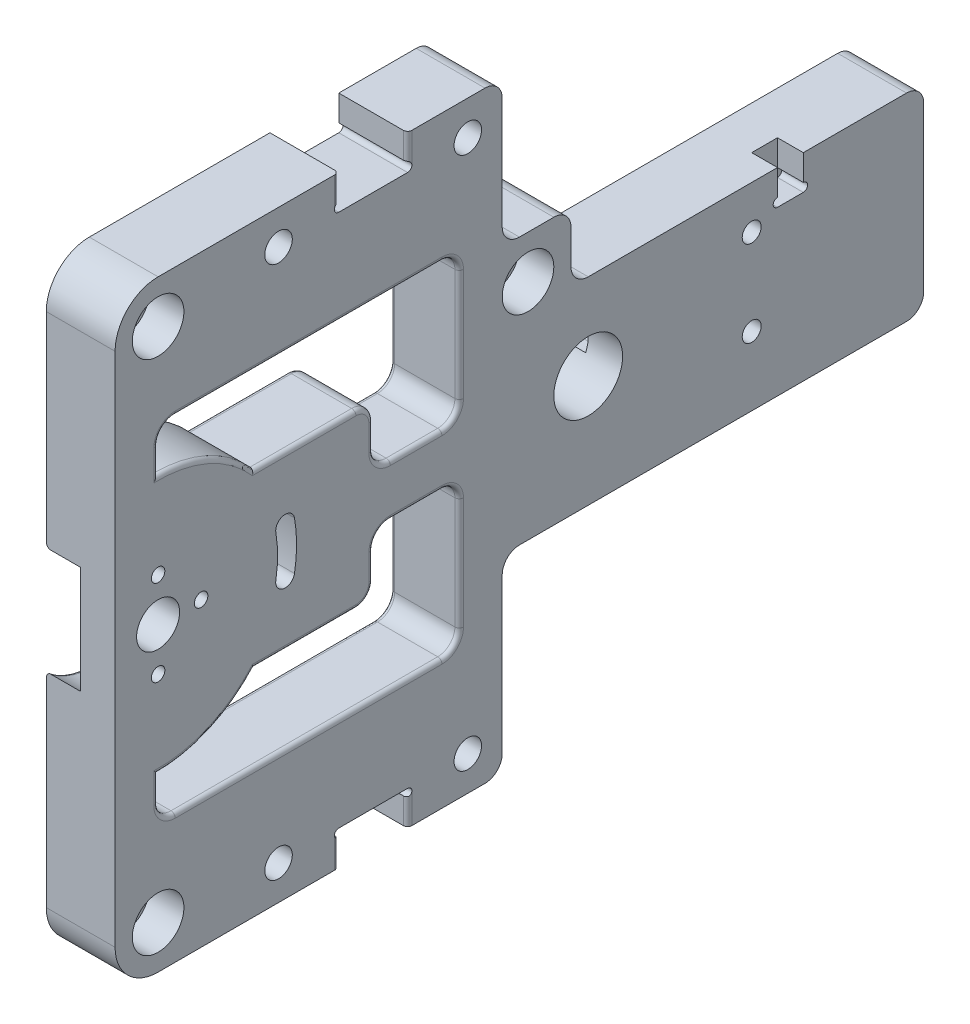
SolidWorks part; units mm, degrees
material "6061 Alloy"
ref_plane "Front Plane" through (0, 0, 0) normal (0, 0, 1) x (1, 0, 0)
ref_plane "Top Plane" through (0, 0, 0) normal (0, 1, 0) x (1, 0, 0)
ref_plane "Right Plane" through (0, 0, 0) normal (1, 0, 0) x (0, 0, -1)
sketch "Sketch1" plane through (0, 0, 0) normal (1, 0, 0) x (0, 0, -1)
  line L0 (-40, 0) -> (40, 0) construction
  line L1 (-40, 35) -> (5, 35)
  line L2 (-40, 35) -> (-40, -35)
  line L3 (-40, -35) -> (5, -35)
  line L4 (54, 10) -> (54, -13)
  line L15 (10, 0) -> (20, 0) construction
  line L18 (54, 10) -> (13, 10)
  line L19 (5, 35) -> (5, 18)
  line L22 (54, -13) -> (5, -13)
  line L23 (5, -35) -> (5, -13)
  line L24 (10, 1.5) -> (20, 1.5)
  line L25 (10, -1.5) -> (20, -1.5)
  line L26 (-25, 35) -> (-40, 35)
  line L33 (5, 18) -> (13, 18)
  line L34 (13, 10) -> (13, 18)
  circle A0 centre (15, 0) radius 4
  arc A1 (10, 1.5) -> (10, -1.5) centre (10, 0) ccw
  arc A2 (20, -1.5) -> (20, 1.5) centre (20, 0) ccw
  circle A3 centre (-35, 0) radius 2.5
  arc A4 (-40, -6.245) -> (-40, 6.245) centre (-35, 0) ccw
  circle A5 centre (-35, 5) radius 0.7835
  circle A6 centre (-30, 0) radius 0.7835
  circle A7 centre (-35, -5) radius 0.7835
  point P0 (0, 0)
  point P24 (15, 0)
  dimension "D9" = 8
  dimension "D10" = 1.5
  dimension "D14" = 5
  dimension "D15" = 16
  dimension "D2" = 1.567
  dimension "D3" = 10
  dimension "D4" = 13
  dimension "D5" = 45
  dimension "D7" = 45
  dimension "D11" = 5
  dimension "D12" = 55
  dimension "D13" = 5
  dimension "D16" = 5
  dimension "D17" = 5
  dimension "D18" = 5
  dimension "D19" = 49
  dimension "D20" = 70
  dimension "D21" = 40
  dimension "D22" = 35
  dimension "D23" = 8
  dimension "D24" = 8
extrude "Boss-Extrude1" add sketch "Sketch1" along normal blind 8 contours L2 L3 L23 L22 L4 L18 L34 L33 L19 L1
extrude "Cut-Extrude1" cut sketch "Sketch1<3>" along normal blind 8 contours A0
sketch "Sketch1<3>" plane through (0, 0, 0) normal (1, 0, 0) x (0, 0, -1) same geometry as "Sketch1"
extrude "Cut-Extrude2" cut sketch "Sketch1<4>" along normal blind 4 contours A2 L24 A1 L25
sketch "Sketch1<4>" plane through (0, 0, 0) normal (1, 0, 0) x (0, 0, -1) same geometry as "Sketch1"
extrude "Cut-Extrude3" cut sketch "Sketch1<5>" along normal blind 4 contours L2 A4 A3 region at (0, 0, 27.2062)
sketch "Sketch1<5>" plane through (0, 0, 0) normal (1, 0, 0) x (0, 0, -1) same geometry as "Sketch1"
extrude "Cut-Extrude4" cut sketch "Sketch1<6>" along normal blind 8 contours A3 | A7 | A6 | A5
sketch "Sketch1<6>" plane through (0, 0, 0) normal (1, 0, 0) x (0, 0, -1) same geometry as "Sketch1"
fillet "Fillet1" radius 2 8 edges at (4, -35, -5) (4, -13, -5) (4, -13, -54) (4, 10, -54) (4, 35, -5) (4, 10, -13) (4, 18, -13) (4, 18, -5)
fillet "Fillet7" radius 5 2 edges at (4, -35, 40) (4, 35, 40)
sketch "Sketch3" plane through (0, 0, 0) normal (-1, 0, 0) x (0, 0, 1)
  line L0 (-54, 8) -> (-54, -11) construction
  line L3 (0, 0) -> (-54, 0) construction
  circle A0 centre (-34, 5) radius 2
  circle A1 centre (-34, -5) radius 2
  circle A2 centre (-34, -5) radius 1.1
  circle A3 centre (-34, 5) radius 1.1
  dimension "D1" = 4
  dimension "D2" = 2.2
  dimension "D5" = 20
  dimension "D6" = 5
  dimension "D7" = 5
extrude "Cut-Extrude6" cut sketch "Sketch3" against normal blind 4 contours A0 | A1
extrude "Cut-Extrude7" cut sketch "Sketch3<3>" against normal blind 8 contours A3 | A2
sketch "Sketch3<3>" plane through (0, 0, 0) normal (-1, 0, 0) x (0, 0, 1) same geometry as "Sketch3"
fillet "Fillet3" radius 0.5 1 edges at (0, 0, 27)
sketch "Sketch4" plane through (0, 0, 0) normal (-1, 0, 0) x (0, 0, 1)
  line L0 (10, 10) -> (10, 3)
  line L1 (40, 6.245) -> (40, -6.245) construction
  line L2 (-44.1333, 0) -> (39.9934, 0) construction
  line L6 (10, 10) -> (23.8197, 10)
  line L7 (10, -10) -> (23.8197, -10)
  line L8 (35, 15) -> (35, 20)
  line L9 (35, 20) -> (0, 20)
  line L10 (0, 20) -> (0, 3)
  line L11 (0, -20) -> (35, -20)
  line L12 (35, -20) -> (35, -15)
  line L13 (10, 3) -> (0, 3)
  line L14 (10, -3) -> (0, -3)
  line L15 (10, -3) -> (10, -10)
  line L16 (0, -3) -> (0, -20)
  arc A2 (35, 15) -> (23.8197, 10) centre (35, 0) ccw
  arc A4 (23.8197, -10) -> (35, -15) centre (35, 0) ccw
  dimension "D2" = 20
  dimension "D4" = 30
  dimension "D1" = 30
  dimension "D3" = 10
  dimension "D5" = 5
  dimension "D6" = 35
  dimension "D7" = 3
  dimension "D8" = 3
extrude "Cut-Extrude8" cut sketch "Sketch4" against normal blind 10
fillet "Fillet4" radius 2 10 edges at (4, -20, 0) (4, -20, 35) (4, -10, 10) (4, -3, 0) (4, -3, 10) (4, 20, 35) (4, 20, 0) (4, 3, 0) (4, 3, 10) (4, 10, 10)
fillet "Fillet5" radius 0.5 48 edges at (8, -16.5, 35) (8, -19.4142, 34.4142) (8, -20, 17.5) (8, -19.4142, 0.5858) (8, -11.5, 0) (8, -3.5858, 0.5858) (8, -3, 5) (8, -3.5858, 9.4142) (8, -6.5, 10) (8, -9.4142, 10.5858) (0, -16.5, 35) (0, -19.4142, 34.4142) (0, -20, 17.5) (0, -19.4142, 0.5858) (0, -11.5, 0) (0, -3.5858, 0.5858) (0, -3, 5) (0, -3.5858, 9.4142) (0, -6.5, 10) (0, -9.4142, 10.5858) (8, 16.5, 35) (8, 19.4142, 34.4142) (8, 20, 17.5) (8, 19.4142, 0.5858) (8, 11.5, 0) (8, 3.5858, 0.5858) (8, 3, 5) (8, 3.5858, 9.4142) (8, 6.5, 10) (8, 9.4142, 10.5858) (0, 16.5, 35) (0, 19.4142, 34.4142) (0, 10, 17.9098) (0, 9.4142, 10.5858) (0, 6.5, 10) (0, 3.5858, 9.4142) (0, 3, 5) (0, 3.5858, 0.5858) (0, 11.5, 0) (0, 19.4142, 0.5858) (8, -10, 17.9098) (8, -13.6931, 28.8763) (0, -10, 17.9098) (0, -13.6931, 28.8763) (8, 10, 17.9098) (8, 13.6931, 28.8763) (0, 13.6931, 28.8763) (0, 20, 17.5)
sketch "Sketch5" plane through (0, 0, 0) normal (-1, 0, 0) x (0, 0, 1)
  line L4 (-5, -33) -> (-5, -15) construction
  line L6 (35, -35) -> (-3, -35) construction
  circle A0 centre (-1, -31) radius 3
  circle A1 centre (-1, -31) radius 1.6
  circle A4 centre (21, -31) radius 3
  circle A5 centre (21, -31) radius 1.6
  dimension "D5" = 6
  dimension "D6" = 3.2
  dimension "D3" = 22
  dimension "D2" = 4
  dimension "D1" = 4
extrude "Cut-Extrude9" cut sketch "Sketch5" against normal blind 4 contours A0 | A4
extrude "Cut-Extrude10" cut sketch "Sketch5<3>" against normal blind 8 contours A1 | A5
sketch "Sketch5<3>" plane through (0, 0, 0) normal (-1, 0, 0) x (0, 0, 1) same geometry as "Sketch5"
sketch "Sketch22" plane through (8, 0, 0) normal (1, 0, 0) x (0, 0, -1)
  line L1 (-14, -31) -> (-6, -31)
  line L2 (-14, -32) -> (-14, -35)
  line L3 (-14, -35) -> (-6, -35)
  line L4 (-6, -32) -> (-6, -35)
  line L5 (-35, -35) -> (3, -35) construction
  circle A0 centre (-21, -31) radius 1.6 construction
  circle A1 centre (1, -31) radius 1.6 construction
  arc A2 (-14, -31) -> (-14, -32) centre (-14, -31.5) ccw
  arc A3 (-6, -32) -> (-6, -31) centre (-6, -31.5) ccw
  dimension "D1" = 7
  dimension "D4" = 1
  dimension "D2" = 7
  dimension "D3" = 4
extrude "Cut-Extrude18" cut sketch "Sketch22" against normal blind 10 contours L1 A3 L4 L3 L2 A2
fillet "Fillet9" radius 0.5 2 edges at (8, -33.5, 14) (8, -33.5, 6)
sketch "Sketch8" plane through (8, 0, 0) normal (1, 0, 0) x (0, 0, -1)
  line L4 (-35, 35) -> (3, 35) construction
  line L5 (-40, 30) -> (-40, -30) construction
  line L6 (-35, -35) -> (-14.5, -35) construction
  line L7 (7, 18) -> (11, 18) construction
  line L8 (13, 12) -> (13, 16) construction
  circle A0 centre (-35, 30) radius 1.6
  circle A1 centre (-35, -30) radius 1.6
  circle A2 centre (8, 13) radius 1.6
  circle A3 centre (-35, 30) radius 3
  circle A4 centre (-35, -30) radius 3
  circle A5 centre (8, 13) radius 3
  dimension "D1" = 3.2
  dimension "D2" = 5
  dimension "D4" = 5
  dimension "D5" = 5
  dimension "D6" = 6
  dimension "D7" = 5
  dimension "D3" = 5
extrude "Cut-Extrude13" cut sketch "Sketch8" against normal blind 10 contours A0 | A2 | A1
extrude "Cut-Extrude14" cut sketch "Sketch8<3>" against normal blind 4 contours A3 | A5 | A4
sketch "Sketch8<3>" plane through (8, 0, 0) normal (1, 0, 0) x (0, 0, -1) same geometry as "Sketch8"
sketch "Sketch16" plane through (0, 0, 0) normal (-1, 0, 0) x (0, 0, 1)
  line L0 (0, 0) -> (35, 0) construction
  arc A4 (20.2279, 2.6047) -> (20.2279, -2.6047) centre (35, 0) ccw construction
  arc A9 (18.2583, 2.952) -> (18.2583, -2.952) centre (35, 0) ccw
  arc A10 (22.1975, 2.2574) -> (22.1975, -2.2574) centre (35, 0) ccw
  arc A11 (22.1975, 2.2574) -> (18.2583, 2.952) centre (20.2279, 2.6047) ccw
  arc A12 (18.2583, -2.952) -> (22.1975, -2.2574) centre (20.2279, -2.6047) ccw
  arc A13 (20.2279, 2.6047) -> (20.2279, -2.6047) centre (35, 0) ccw construction
  arc A14 (19.1446, 2.7957) -> (19.1446, -2.7957) centre (35, 0) ccw
  arc A15 (21.3112, 2.4137) -> (21.3112, -2.4137) centre (35, 0) ccw
  arc A16 (21.3112, 2.4137) -> (19.1446, 2.7957) centre (20.2279, 2.6047) ccw
  arc A17 (19.1446, -2.7957) -> (21.3112, -2.4137) centre (20.2279, -2.6047) ccw
  point P3 (20, 0)
  point P17 (20, 0)
  dimension "D2" = 2
  dimension "D4" = 1.1
  dimension "D1" = 20
  dimension "D3" = 15
extrude "Cut-Extrude15" cut sketch "Sketch16" against normal blind 4 contours A11 A9 A12 A10
extrude "Cut-Extrude16" cut sketch "Sketch16<3>" against normal blind 8 contours A16 A14 A17 A15
sketch "Sketch16<3>" plane through (0, 0, 0) normal (-1, 0, 0) x (0, 0, 1) same geometry as "Sketch16"
hole_wizard "Ø3.0mm Dowel Hole2" positions "Sketch17" profile "Sketch18" hole size "Ø3.0" standard "ANSI Metric"
sketch "Sketch17" plane through (0, 0, 0) normal (-1, 0, 0) x (0, 0, 1)
  line L9 (40, -6.8739) -> (40, -30) construction
  line L10 (35, -35) -> (14, -35) construction
  line L12 (35, 35) -> (-3, 35) construction
  line L13 (40, 30) -> (40, 6.8739) construction
  point P0 (30, -30)
  point P2 (30, 30)
  dimension "D1" = 5
  dimension "D2" = 10
  dimension "D3" = 10
  dimension "D4" = 5
sketch "Sketch18" plane through (0, -30, 30) normal (0, 1, 0) x (0, 0, 1)
  line L0 (0, 0) -> (0, 5.9013)
  line L1 (0, 5.9013) -> (1.5, 5)
  line L2 (1.5, 5) -> (1.5, 0)
  line L5 (1.5, 0) -> (0, 0)
  line L10 (0, 5.9013) -> (-1.5, 5) construction
  line L11 (0, -6.35) -> (0, 107.95) construction
  dimension "Hole Dia." = 3
  dimension "Hole Depth" = 5
  dimension "Drill Angle" = 118
sketch "Sketch21" plane through (0, -13, 0) normal (0, -1, 0) x (1, 0, 0)
  line L1 (8, -54) -> (0, -54) construction
  line L2 (0, -52) -> (0, -7) construction
  circle A0 centre (4, -27) radius 1.2295
  circle A1 centre (4, -42) radius 1.2295
  dimension "D2" = 12
  dimension "D3" = 15
  dimension "D4" = 2.459
  dimension "D1" = 4
extrude "Cut-Extrude17" cut sketch "Sketch21" against normal blind 10
mirror "Mirror1" about plane through (0, 0, 0) normal (0, 1, 0) of "Fillet9", "Cut-Extrude18", "Cut-Extrude10", "Cut-Extrude9"
sketch "Sketch25" plane through (8, 0, 0) normal (1, 0, 0) x (0, 0, -1)
  line L1 (37, 10) -> (40, 10)
  line L2 (37, 10) -> (37, 7)
  line L3 (37, 6) -> (40, 6)
  line L4 (40, 10) -> (40, 7)
  line L5 (52, 10) -> (15, 10) construction
  circle A0 centre (34, 5) radius 1.1 construction
  arc A1 (37, 7) -> (37, 6) centre (37, 6.5) ccw
  arc A2 (40, 6) -> (40, 7) centre (40, 6.5) ccw
  dimension "D1" = 3
  dimension "D4" = 1
  dimension "D2" = 3
  dimension "D3" = 4
extrude "Cut-Extrude20" cut sketch "Sketch25" against normal blind 3
sketch "Sketch26" plane through (0, 0, 0) normal (-1, 0, 0) x (0, 0, 1)
  line L0 (-52, -13) -> (-7, -13) construction
  line L1 (-37, -13) -> (-32, -13)
  line L2 (-37, -14) -> (-37, -16.9)
  line L3 (-37, -16.9) -> (-32, -16.9)
  line L4 (-32, -14) -> (-32, -16.9)
  line L5 (-54, 8) -> (-54, -11) construction
  arc A0 (-37, -14) -> (-37, -13) centre (-37, -13.5) ccw
  arc A1 (-32, -13) -> (-32, -14) centre (-32, -13.5) ccw
  point P12 (0, 0)
  dimension "D4" = 1
  dimension "D1" = 17
  dimension "D2" = 5
  dimension "D3" = 3.9
extrude "Boss-Extrude2" add sketch "Sketch26" against normal blind 4
fillet "Fillet11" radius 1 6 edges at (2, -16.9, -32) (4, -16.9, -34.5) (2, -16.9, -37) (0, -16.9, -34.5) (4, -15.45, -32) (4, -15.45, -37)
